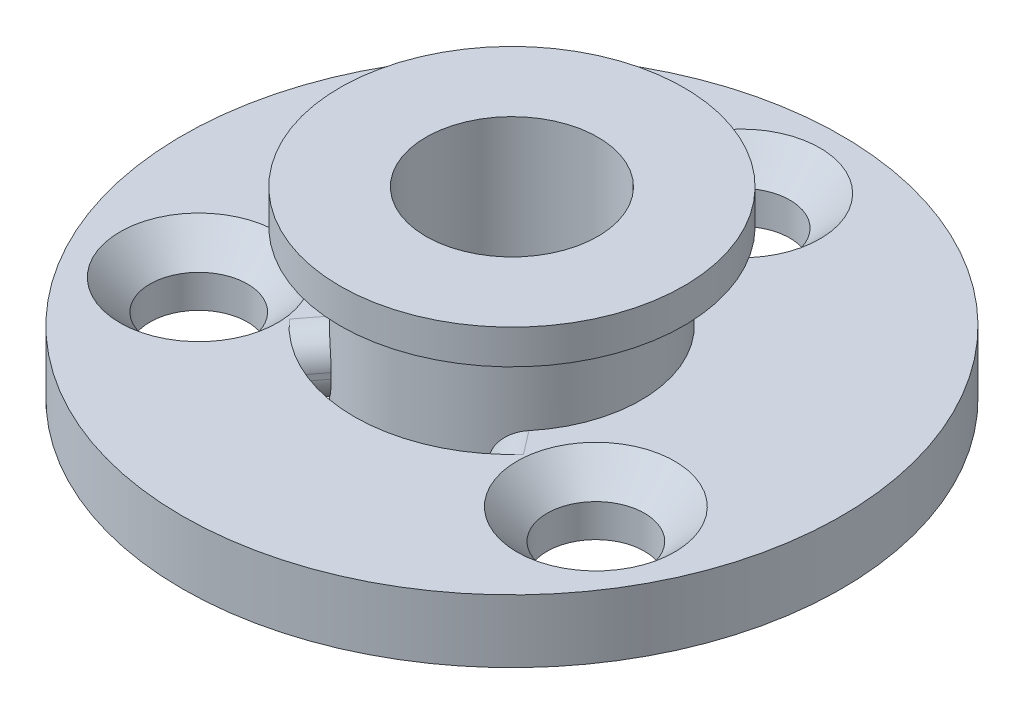
SolidWorks part; units mm, degrees
ref_plane "Plan de face" through (0, 0, 0) normal (0, 0, 1) x (1, 0, 0)
ref_plane "Plan de dessus" through (0, 0, 0) normal (0, 1, 0) x (1, 0, 0)
ref_plane "Plan de droite" through (0, 0, 0) normal (1, 0, 0) x (0, 0, -1)
sketch "Esquisse1" plane through (0, 0, 0) normal (0, 0, 1) x (1, 0, 0)
  line L0 (0, 4.6899) -> (0, -3.9873) construction
  line L1 (3, -3.2) -> (3, 3.2)
  line L2 (3, 3.2) -> (6, 3.2)
  line L3 (6, 3.2) -> (6, 2)
  line L4 (6, 2) -> (4.5, 2)
  line L5 (4.5, 2) -> (4.5, -1)
  line L6 (4.5, -1) -> (11.5, -1)
  line L7 (11.5, -1) -> (11.5, -3.2)
  line L8 (11.5, -3.2) -> (3, -3.2)
  point P5 (4.5, 0.5)
  point P12 (3, 0)
  dimension "D1" = 1.2
  dimension "D2" = 2.2
  dimension "D3" = 3
  dimension "D4" = 3
  dimension "D5" = 1.5
  dimension "D6" = 1.5
  dimension "D7" = 11.5
revolve "Révolution1" add sketch "Esquisse1" angle 360 about L0
sketch "Esquisse2" plane through (0, -1, 0) normal (0, 1, 0) x (1, 0, 0)
  line L0 (0, 0) -> (0, 8) construction
  line L1 (0, 0) -> (6.9282, -4) construction
  line L2 (0, 0) -> (-6.9282, -4) construction
  circle A0 centre (0, 0) radius 8 construction
  circle A1 centre (0, 8) radius 1.7 construction
  circle A2 centre (0, 8) radius 2.85 construction
  circle A3 centre (6.9282, -4) radius 2.85 construction
  circle A4 centre (6.9282, -4) radius 1.7 construction
  circle A5 centre (-6.9282, -4) radius 2.85 construction
  circle A6 centre (-6.9282, -4) radius 1.7 construction
  point P14 (0, 0)
  dimension "D1" = 16
  dimension "D2" = 3.4
  dimension "D3" = 5.7
  dimension "D4" = 3
sketch "Esquisse5" plane through (0, -1, 0) normal (0, 1, 0) x (1, 0, 0)
  point P0 (-6.9282, -4)
  point P3 (6.9282, -4)
  point P6 (0, 8)
hole_wizard "CSK for M3 Flat Head Machine Screw1" positions "Esquisse5" profile "Esquisse4" countersink size "M3" standard "ANSI Metric" end condition through all
sketch "Esquisse4" plane through (-6.9282, -1, 4) normal (1, 0, 0) x (0, 0, 1)
  line L0 (0, 0) -> (0, 2.2)
  line L1 (0, 2.2) -> (1.7, 2.2)
  line L2 (1.7, 2.2) -> (1.7, 1.05)
  line L3 (1.7, 1.05) -> (2.75, 0)
  line L5 (2.75, 0) -> (0, 0)
  line L6 (-1.7, 1.05) -> (-2.75, 0) construction
  line L11 (0, -6.35) -> (0, 107.95) construction
  dimension "Thru Hole Dia." = 3.4
  dimension "Thru Hole Depth" = 2.2
  dimension "Near C'Sink Dia." = 5.5
  dimension "Near C'Sink Angle" = 90
sketch "Esquisse6" plane through (0, -1, 0) normal (0, 1, 0) x (1, 0, 0)
  line L0 (2.7394, -3.5701) -> (3.3482, -4.3634)
  line L1 (-2.7394, -3.5701) -> (-3.3482, -4.3634)
  line L2 (0, 0) -> (0, -11.5) construction
  arc A0 (2.7394, -3.5701) -> (-2.7394, -3.5701) centre (0, 0) cw
  arc A1 (-3.3482, -4.3634) -> (3.3482, -4.3634) centre (0, 0) ccw
  circle A2 centre (0, 0) radius 4.5 construction
  circle A3 centre (0, 0) radius 11.5 construction
  dimension "D1" = 1
  dimension "D2" = 37.5
  dimension "D3" = 37.5
extrude "Enlèv. mat.-Extru.1" cut sketch "Esquisse6" against normal through all
fillet "Congé1" radius 1 4 edges at (3.0438, -3.2, 3.9668) (-3.0438, -3.2, 3.9668) (-3.0438, -1, 3.9668) (3.0438, -1, 3.9668)
